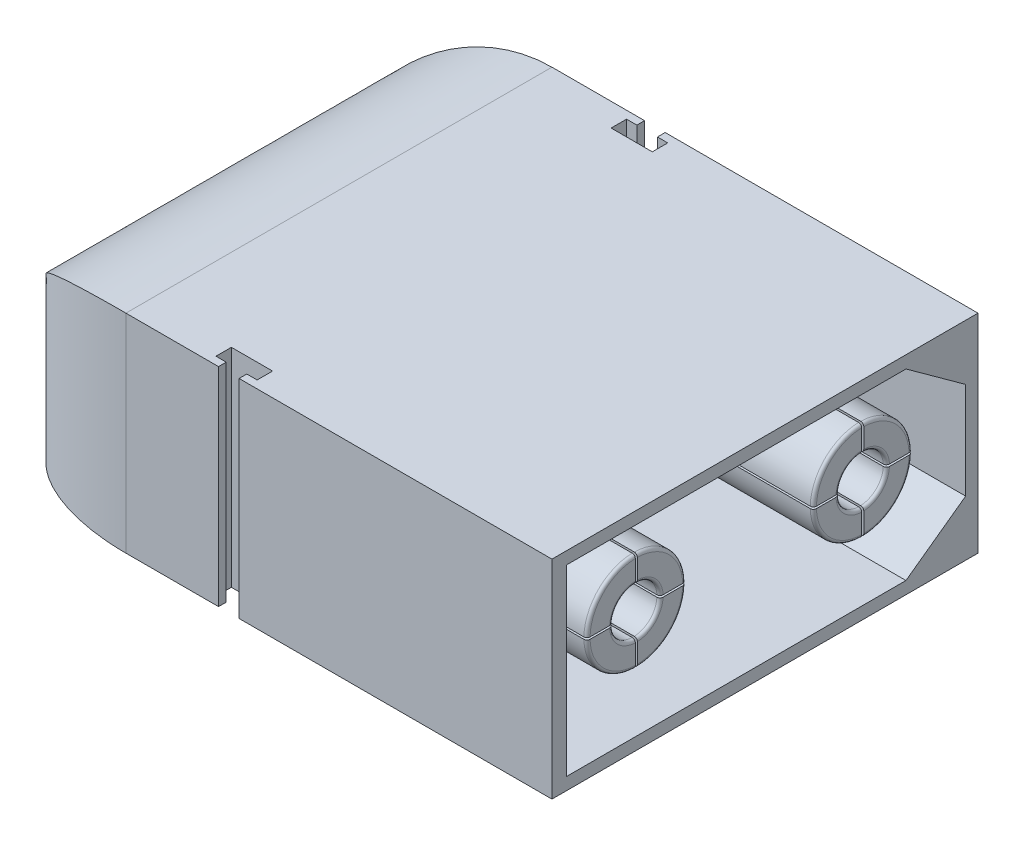
SolidWorks part; units mm, degrees
ref_plane "Front Plane" through (0, 0, 0) normal (0, 0, 1) x (1, 0, 0)
ref_plane "Top Plane" through (0, 0, 0) normal (0, 1, 0) x (1, 0, 0)
ref_plane "Right Plane" through (0, 0, 0) normal (1, 0, 0) x (0, 0, -1)
sketch "Sketch1" plane through (0, 0, 0) normal (0, 1, 0) x (1, 0, 0)
  line L0 (-7.1, 10.35) -> (-7.1, -10.35)
  line L1 (-13.6, 10.35) -> (-2.6, 10.35)
  line L2 (-13.6, 10.35) -> (-13.6, -10.35)
  line L3 (-13.6, -10.35) -> (-2.6, -10.35)
  line L4 (13.6, 10.35) -> (13.6, -10.35)
  line L5 (-13.6, 10.35) -> (13.6, -10.35) construction
  line L6 (-13.6, -10.35) -> (13.6, 10.35) construction
  line L7 (-7.1, -9.6) -> (-2.1, -9.6) construction
  line L8 (-2.1, -9.975) -> (-2.1, -10.35) construction
  line L9 (-3.1, -9.225) -> (-1.1, -9.225)
  line L10 (-3.1, -9.225) -> (-3.1, -9.975)
  line L11 (-3.1, -9.975) -> (-2.6, -9.975)
  line L12 (-1.1, -9.225) -> (-1.1, -9.975)
  line L13 (-3.1, -9.225) -> (-1.1, -9.975) construction
  line L14 (-3.1, -9.975) -> (-1.1, -9.225) construction
  line L15 (-2.6, -9.975) -> (-2.6, -10.35)
  line L16 (-1.6, -9.975) -> (-1.6, -10.35)
  line L17 (-1.6, -9.975) -> (-1.1, -9.975)
  line L18 (-1.6, -10.35) -> (13.6, -10.35)
  line L19 (13.6, 0) -> (-13.6, 0) construction
  line L20 (-2.6, 9.975) -> (-2.6, 10.35)
  line L21 (-3.1, 9.975) -> (-2.6, 9.975)
  line L22 (-3.1, 9.225) -> (-3.1, 9.975)
  line L23 (-3.1, 9.225) -> (-1.1, 9.225)
  line L24 (-1.1, 9.225) -> (-1.1, 9.975)
  line L25 (-1.6, 9.975) -> (-1.1, 9.975)
  line L26 (-1.6, 9.975) -> (-1.6, 10.35)
  line L27 (-1.6, 10.35) -> (13.6, 10.35)
  point P0 (0, 0)
  dimension "D1" = 27.2
  dimension "D2" = 20.7
  dimension "D3" = 20.7
  dimension "D4" = 5
  dimension "D5" = 2
  dimension "D6" = 0.75
  dimension "D7" = 0.75
  dimension "D8" = 0.5
  dimension "D9" = 0.5
extrude "Boss-Extrude1" add sketch "Sketch1" along normal blind 10.1 contours L27 L26 L25 L24 L23 L22 L21 L20 L1 L0 L3 L15 L11 L10 L9 L12 L17 L16 L18 L4 | L2 L3 L0 L1
fillet "Fillet1" radius 4 1 edges at (-13.6, 10.1, 0)
fillet "Fillet2" radius 6.5 2 edges
sketch "Sketch2" plane through (13.6, 0, 0) normal (1, 0, 0) x (0, 0, -1)
  line L0 (-9.65, 9.5) -> (-9.65, 0.6)
  line L1 (-9.65, 0.6) -> (6.85, 0.6)
  line L2 (9.75, 2.7) -> (9.75, 7.4)
  line L3 (6.85, 9.5) -> (-9.65, 9.5)
  line L4 (-10.35, 0) -> (10.35, 0)
  line L5 (10.35, 0) -> (10.35, 10.1)
  line L6 (10.35, 10.1) -> (-10.35, 10.1)
  line L7 (-10.35, 10.1) -> (-10.35, 0)
  line L8 (-10.35, 0) -> (10.35, 0) construction
  line L9 (10.35, 0) -> (10.35, 10.1) construction
  line L10 (10.35, 10.1) -> (-10.35, 10.1) construction
  line L11 (-10.35, 10.1) -> (-10.35, 0) construction
  line L12 (9.75, 9.5) -> (-10.35, 9.5) construction
  line L13 (-9.65, 10.1) -> (-9.65, 0) construction
  line L14 (-10.35, 0.6) -> (9.75, 0.6) construction
  line L15 (6.85, 9.5) -> (9.75, 7.4)
  line L16 (-9.65, 5.05) -> (9.75, 5.05) construction
  line L17 (6.85, 0.6) -> (9.75, 2.7)
  line L18 (9.75, 0.6) -> (9.75, 9.5) construction
  dimension "D4" = 2.7
  dimension "D5" = 3.5
  dimension "D1" = 0
  dimension "D2" = 0.7
  dimension "D3" = 0.6
extrude "Cut-Extrude1" cut sketch "Sketch2" against normal blind 12.8
sketch "Sketch3" plane through (0.8, 0, 0) normal (1, 0, 0) x (0, 0, -1)
  line L0 (5.5, 7.4495) -> (5.5, 6.1989)
  line L3 (5.6, 7.4495) -> (5.6, 6.1989)
  line L4 (-10.35, 10.1) -> (-10.35, 0) construction
  line L5 (-5.5, 7.4495) -> (-5.5, 6.1989)
  line L6 (-5.4, 7.4495) -> (-5.4, 6.1989)
  line L7 (-3.0505, 5.1) -> (-4.3011, 5.1)
  line L8 (-3.0505, 5) -> (-4.3011, 5)
  line L9 (7.9495, 5.1) -> (6.6989, 5.1)
  line L10 (-5.4, 2.6505) -> (-5.4, 3.9011)
  line L11 (-5.5, 2.6505) -> (-5.5, 3.9011)
  line L12 (7.9495, 5) -> (6.6989, 5)
  line L13 (-7.8495, 5) -> (-6.5989, 5)
  line L14 (-7.8495, 5.1) -> (-6.5989, 5.1)
  line L15 (5.6, 2.6505) -> (5.6, 3.9011)
  line L16 (5.5, 2.6505) -> (5.5, 3.9011)
  line L17 (3.1505, 5) -> (4.4011, 5)
  line L18 (3.1505, 5.1) -> (4.4011, 5.1)
  arc A0 (-3.0505, 5.1) -> (-5.4, 7.4495) centre (-5.45, 5.05) ccw
  arc A2 (-4.3011, 5.1) -> (-5.4, 6.1989) centre (-5.45, 5.05) ccw
  arc A4 (-5.5, 7.4495) -> (-7.8495, 5.1) centre (-5.45, 5.05) ccw
  arc A5 (-5.5, 6.1989) -> (-6.5989, 5.1) centre (-5.45, 5.05) ccw
  arc A6 (-5.4, 3.9011) -> (-4.3011, 5) centre (-5.45, 5.05) ccw
  arc A7 (-5.4, 2.6505) -> (-3.0505, 5) centre (-5.45, 5.05) ccw
  arc A8 (-6.5989, 5) -> (-5.5, 3.9011) centre (-5.45, 5.05) ccw
  arc A9 (-7.8495, 5) -> (-5.5, 2.6505) centre (-5.45, 5.05) ccw
  arc A10 (7.9495, 5.1) -> (5.6, 7.4495) centre (5.55, 5.05) ccw
  arc A11 (6.6989, 5.1) -> (5.6, 6.1989) centre (5.55, 5.05) ccw
  arc A12 (5.5, 7.4495) -> (3.1505, 5.1) centre (5.55, 5.05) ccw
  arc A13 (5.5, 6.1989) -> (4.4011, 5.1) centre (5.55, 5.05) ccw
  arc A14 (5.6, 3.9011) -> (6.6989, 5) centre (5.55, 5.05) ccw
  arc A15 (5.6, 2.6505) -> (7.9495, 5) centre (5.55, 5.05) ccw
  arc A16 (4.4011, 5) -> (5.5, 3.9011) centre (5.55, 5.05) ccw
  arc A17 (3.1505, 5) -> (5.5, 2.6505) centre (5.55, 5.05) ccw
  point P35 (5.55, 5.05)
  point P41 (-5.45, 5.05)
  dimension "D1" = 4.8
  dimension "D2" = 2
  dimension "D5" = 2.3
  dimension "D4" = 4.9
  dimension "D9" = 4
extrude "Boss-Extrude2" add sketch "Sketch3" along normal blind 12
fillet "Fillet3" radius 0.15 16 edges at (12.8, 5.8632, 6.2632) (12.8, 4.2368, 6.2632) (12.8, 4.2368, 4.6368) (12.8, 5.8632, 4.6368) (12.8, 5.8632, -6.3632) (12.8, 5.8632, -4.7368) (12.8, 4.2368, -4.7368) (12.8, 4.2368, -6.3632) (12.8, 3.3529, -7.2471) (12.8, 6.7471, -7.2471) (12.8, 6.7471, -3.8529) (12.8, 3.3529, -3.8529) (12.8, 3.3529, 3.7529) (12.8, 3.3529, 7.1471) (12.8, 6.7471, 3.7529) (12.8, 6.7471, 7.1471)
sketch "Sketch4" plane through (0, 0, 0) normal (0, -1, 0) x (1, 0, 0)
  line L0 (-13.6, -6.85) -> (-13.6, 6.85) construction
  line L1 (-7.1, -10.35) -> (-2.6, -10.35) construction
  line L2 (-7.1, 10.35) -> (-2.6, 10.35) construction
  circle A0 centre (-11.1, -5.65) radius 1.75
  circle A1 centre (-11.1, 5.65) radius 1.75
  point P8 (0, 0)
  point P10 (-11.2773, 4.4619)
  dimension "D1" = 3.5
  dimension "D4" = 3.5
  dimension "D2" = 2.5
  dimension "D3" = 4.7
  dimension "D5" = 2.5
  dimension "D6" = 4.7
extrude "Boss-Extrude3" add sketch "Sketch4" along normal blind 2.7
fillet "Fillet4" radius 0.15 2 edges at (-11.1, -2.7, -7.4) (-11.1, -2.7, 3.9)
